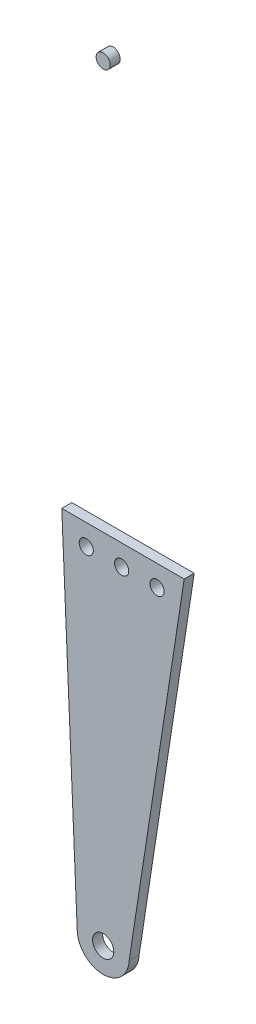
SolidWorks part; units mm, degrees
ref_plane "Front Plane" through (0, 0, 0) normal (0, 0, 1) x (1, 0, 0)
ref_plane "Top Plane" through (0, 0, 0) normal (0, 1, 0) x (1, 0, 0)
ref_plane "Right Plane" through (0, 0, 0) normal (1, 0, 0) x (0, 0, -1)
sketch "Sketch1" plane through (0, 0, 0) normal (0, 0, 1) x (1, 0, 0)
  line L0 (58.9105, 262.9177) -> (58.9105, -62.0823) construction
  line L1 (41.3586, 89.8031) -> (47.9105, -62.0823)
  line L2 (36.9105, 192.9177) -> (42.087, 72.9177) construction
  line L3 (47.9105, -62.0823) -> (58.9105, -62.0823) construction
  line L4 (58.9105, -62.0823) -> (69.9105, -62.0823) construction
  line L5 (93.2727, 89.8031) -> (69.9105, -62.0823)
  line L6 (90.6755, 72.9177) -> (105.7494, 170.9177) construction
  line L7 (41.3586, 89.8031) -> (93.2727, 89.8031)
  circle A0 centre (58.9105, -62.0823) radius 4.5
  circle A1 centre (58.9105, 262.9177) radius 3 construction
  circle A2 centre (58.9105, 262.9177) radius 3
  arc A3 (47.9105, -62.0823) -> (69.9105, -62.0823) centre (58.9105, -61.6078) ccw
  point P12 (0, 0)
  point P15 (0, 0)
  point P16 (0, 0)
  dimension "D1" = 9
  dimension "D2" = 325
  dimension "D3" = 151.8854
  dimension "D4" = 11
extrude "Boss-Extrude1" add sketch "Sketch1" along normal up to surface (4.25 mm away)
sketch "Sketch2" plane through (0, 0, 4.25) normal (0, 0, 1) x (1, 0, 0)
  circle A0 centre (51.7512, 80.9177) radius 3
  circle A1 centre (66.7512, 80.9177) radius 3
  circle A2 centre (81.7512, 80.9177) radius 3
  point P8 (82.6806, 73.4922)
  point P9 (81.7512, 80.9177)
  dimension "D1" = 6
  dimension "D2" = 6
  dimension "D3" = 6
extrude "Cut-Extrude1" cut sketch "Sketch2" against normal blind 10
